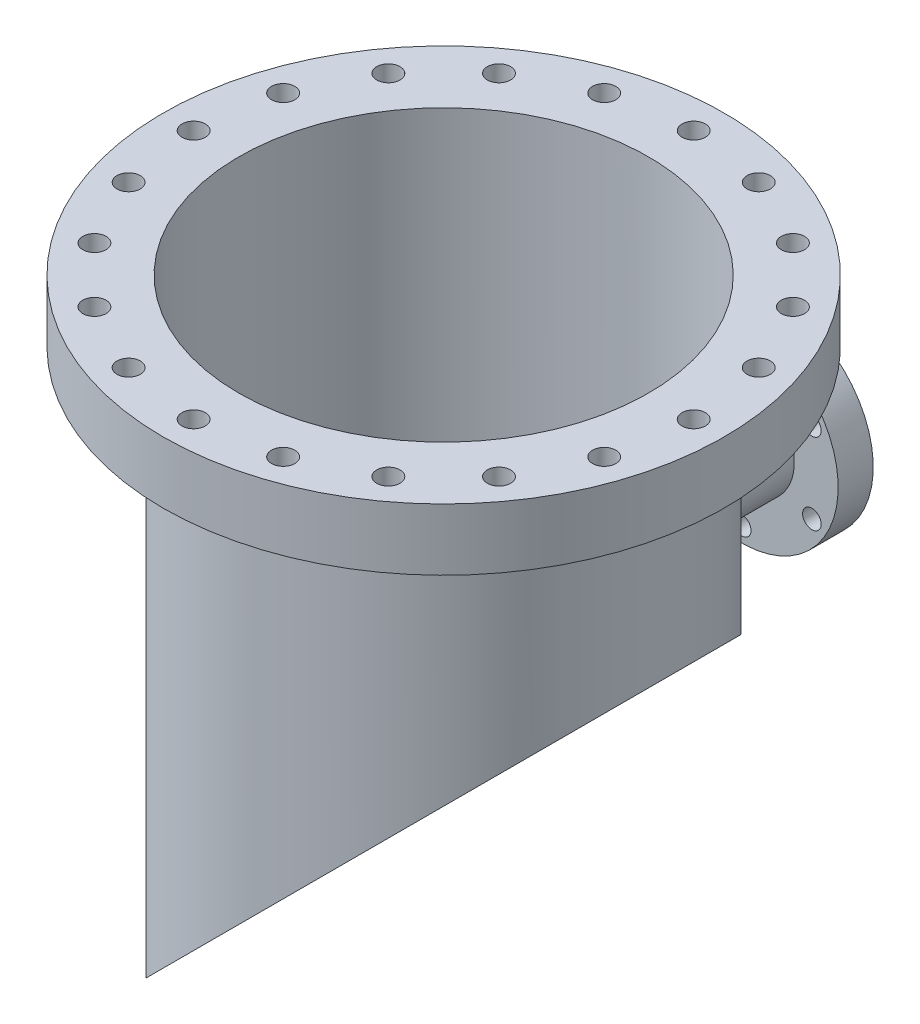
SolidWorks part; units mm, degrees
ref_plane "Front Plane" through (0, 0, 0) normal (0, 0, 1) x (1, 0, 0)
ref_plane "Top Plane" through (0, 0, 0) normal (0, 1, 0) x (1, 0, 0)
ref_plane "Right Plane" through (0, 0, 0) normal (1, 0, 0) x (0, 0, -1)
sketch "Sketch1" plane through (0, 0, 0) normal (0, 1, 0) x (1, 0, 0)
  circle A0 centre (0, 0) radius 76.2
extrude "Extrude-Thin1" add sketch "Sketch1" against normal mid plane 220.472 thin thin type one direction reverse wall 2.032
sketch "Sketch2" plane through (0, 0, 0) normal (0, 0, 1) x (1, 0, 0)
  line L0 (-76.2, -110.236) -> (76.2, 42.164)
  line L1 (76.2, 42.164) -> (76.2, -110.236)
  line L2 (76.2, -110.236) -> (-76.2, -110.236)
extrude "Cut-Extrude1" cut sketch "Sketch2" against normal through all and the other way through all
ref_plane "Plane1" through (17.018, -17.018, 0) normal (0.7071, -0.7071, 0) x (0.7071, 0.7071, 0)
sketch "Sketch6" plane through (0, 0, 0) normal (1, 0, 0) x (0, 0, -1)
  line L0 (0, 0) -> (0, -126.6701)
sketch "Sketch9" plane through (17.018, -17.018, 0) normal (0.7071, -0.7071, 0) x (0.7071, 0.7071, 0)
  line L0 (0, 0) -> (-89.5693, 0) construction
  point P0 (-24.0671, 0)
sketch "Sketch10" plane through (0, 0, 0) normal (1, 0, 0) x (0, 0, -1)
  line L0 (0, 0) -> (78.8279, 0)
sketch "Sketch11" plane through (0, 0, 0) normal (0, 0, 1) x (1, 0, 0)
  line L0 (0, 0) -> (0, 110.236)
  line L1 (74.168, 110.236) -> (-74.168, 110.236) construction
ref_plane "Plane2" through (0, 110.236, 0) normal (0, 1, 0) x (-1, 0, 0)
sketch "Sketch12" plane through (0, 110.236, 0) normal (0, 1, 0) x (-1, 0, 0)
  circle A0 centre (0, 0) radius 101.6
extrude "Extrude1" add sketch "Sketch12" along normal blind 22.352
sketch "Sketch14" plane through (0, 110.236, 0) normal (0, 1, 0) x (-1, 0, 0)
  circle A0 centre (0, 0) radius 74.168
  dimension "D1" = 148.336
extrude "Cut-Extrude2" cut sketch "Sketch14" along normal through all
sketch "Sketch15" plane through (0, 110.236, 0) normal (0, 1, 0) x (-1, 0, 0)
  circle A0 centre (0, 90.551) radius 4.2164
extrude "Cut-Extrude4" cut sketch "Sketch15" along normal blind 22.352
ref_axis "Axis1" through (0, 0, -78.8279) along (0, 0, 1)
ref_axis "Axis2" through (0, 110.236, 0) along (0, -1, 0)
pattern_circular "CirPattern1" count 20 over 360 about axis through (0, 110.236, 0) along (0, -1, 0) of "Cut-Extrude4"
sketch "Sketch16" plane through (0, 0, 0) normal (0, 0, 1) x (1, 0, 0)
  line L0 (0, 0) -> (0, -126.6701) construction
  line L1 (0, -34.036) -> (-107.95, -34.036)
  point P0 (0, -34.036)
  dimension "D1" = 34.036
  dimension "D2" = 107.95
ref_plane "Plane3" through (-107.95, -34.036, 0) normal (-1, 0, 0) x (0, 0, 1)
sketch "Sketch17" plane through (-107.95, -34.036, 0) normal (-1, 0, 0) x (0, 0, 1)
  circle A0 centre (0, 0) radius 19.05
extrude "Extrude2" [suppressed] add sketch "Sketch17" against normal up to body separate body
sketch "Sketch18" plane through (-107.95, -34.036, 0) normal (-1, 0, 0) x (0, 0, 1)
  circle A0 centre (0, 0) radius 34.925
  dimension "D1" = 69.85
extrude "Extrude3" [suppressed] add sketch "Sketch18" along normal blind 12.7
sketch "Sketch20" plane through (-107.95, -34.036, 0) normal (-1, 0, 0) x (0, 0, 1)
  circle A0 centre (0, 0) radius 17.399
  dimension "D1" = 34.798
extrude "Cut-Extrude5" [suppressed] cut sketch "Sketch20" against normal up to vertex and the other way through all
sketch "Sketch21" plane through (-107.95, -34.036, 0) normal (-1, 0, 0) x (0, 0, 1)
  circle A0 centre (0, 29.337) radius 3.3655
extrude "Cut-Extrude6" [suppressed] cut sketch "Sketch21" along normal blind 12.7
ref_axis "Axis3" through (-107.95, -34.036, 0) along (1, 0, 0)
pattern_circular "CirPattern2" [suppressed] count 6 over 360 about axis through (-107.95, -34.036, 0) along (1, 0, 0) of bodies 111
sketch "Sketch22" plane through (0, 0, 0) normal (1, 0, 0) x (0, 0, -1)
  line L0 (0, 0) -> (0, 110.236) construction
  point P0 (0, 0)
  point P1 (0, 29.464)
  dimension "D1" = 29.464
  dimension "D2" = 63.5
sketch "Sketch23" plane through (0, 0, 0) normal (1, 0, 0) x (0, 0, -1)
  line L0 (0, 29.464) -> (107.95, 29.464)
  line L1 (0, 0) -> (78.8279, 0) construction
  dimension "D1" = 107.95
  dimension "D2" = 29.464
ref_plane "Plane4" through (0, 29.464, -107.95) normal (0, 0, -1) x (-1, 0, 0)
sketch "Sketch24" plane through (0, 29.464, -107.95) normal (0, 0, -1) x (-1, 0, 0)
  circle A0 centre (0, 0) radius 19.05
extrude "Extrude4" add sketch "Sketch24" against normal up to body separate body
sketch "Sketch25" plane through (0, 29.464, -107.95) normal (0, 0, -1) x (-1, 0, 0)
  circle A0 centre (0, 0) radius 34.925
  dimension "D1" = 69.85
extrude "Extrude5" add sketch "Sketch25" along normal blind 12.7
sketch "Sketch26" plane through (0, 29.464, -107.95) normal (0, 0, -1) x (-1, 0, 0)
  circle A0 centre (0, 0) radius 17.399
  dimension "D1" = 34.798
extrude "Cut-Extrude7" cut sketch "Sketch26" against normal up to vertex (107.95 mm away) and the other way blind 12.7 up to point (0, 29.464, 0)
sketch "Sketch27" plane through (0, 29.464, -107.95) normal (0, 0, -1) x (-1, 0, 0)
  circle A0 centre (0, 29.337) radius 3.3655
extrude "Cut-Extrude9" cut sketch "Sketch27" along normal blind 12.7
ref_axis "Axis4" through (0, 29.464, -107.95) along (0, 0, 1)
pattern_circular "CirPattern3" count 6 over 360 about axis through (0, 29.464, -107.95) along (0, 0, 1) of "Cut-Extrude9"
sketch "Sketch28" plane through (0, 0, 0) normal (1, 0, 0) x (0, 0, -1)
  line L0 (0, 84.836) -> (-94.3998, 84.836)
  line L1 (0, 0) -> (0, 110.236) construction
  line L2 (-101.6, 110.236) -> (101.6, 110.236) construction
  dimension "D1" = 25.4
sketch "Sketch29" plane through (0, 0, 0) normal (1, 0, 0) x (0, 0, -1)
  line L0 (0, -12.7) -> (70.4555, -12.7)
  line L1 (0, 0) -> (0, -126.6701) construction
  dimension "D1" = 12.7
sketch "Sketch30" plane through (0, 0, 0) normal (1, 0, 0) x (0, 0, -1)
  line L0 (0, 32.258) -> (-47.081, 32.258)
  line L2 (0, 0) -> (0, 110.236) construction
  dimension "D1" = 2.794
